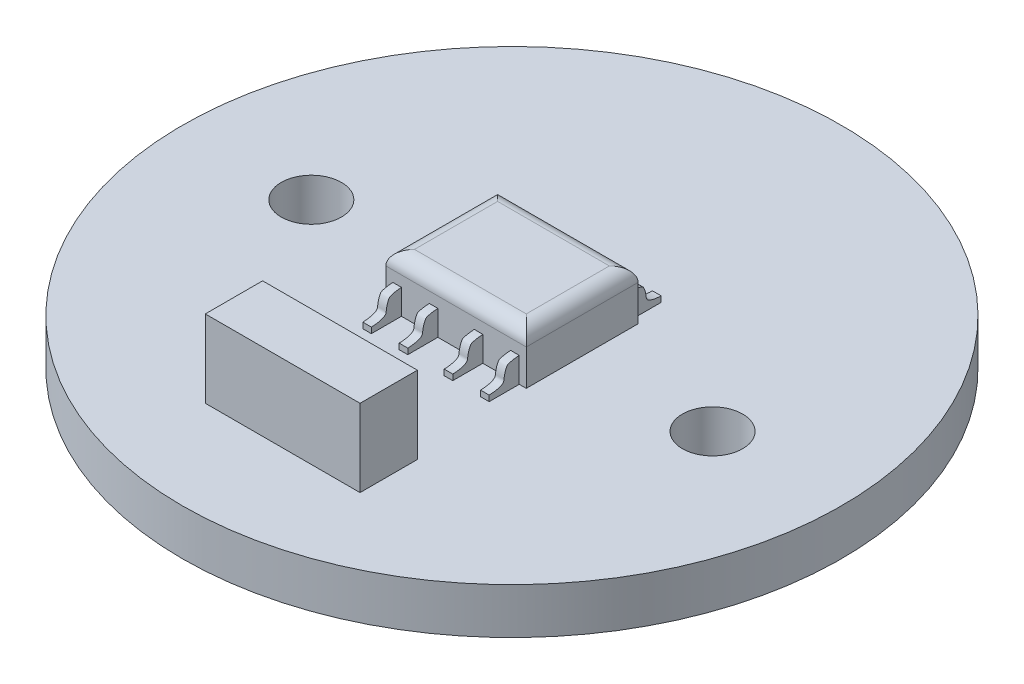
SolidWorks part; units mm, degrees
ref_plane "Front Plane" through (0, 0, 0) normal (0, 0, 1) x (1, 0, 0)
ref_plane "Top Plane" through (0, 0, 0) normal (0, 1, 0) x (1, 0, 0)
ref_plane "Right Plane" through (0, 0, 0) normal (1, 0, 0) x (0, 0, -1)
sketch "Sketch1" plane through (0, 0, 0) normal (0, 1, 0) x (1, 0, 0)
  circle A0 centre (0, 0) radius 11.5
  circle A1 centre (0, 0) radius 7 construction
  circle A2 centre (-7, 0) radius 1.05
  circle A3 centre (7, 0) radius 1.05
  dimension "D1" = 23
  dimension "D2" = 14
  dimension "D3" = 2.1
extrude "Boss-Extrude1" add sketch "Sketch1" along normal blind 1.6
sketch "Sketch2" plane through (0, 1.6, 0) normal (0, 1, 0) x (1, 0, 0)
  line L0 (0, -0.88) -> (0, 0.88) construction
  line L1 (-2.45, 1.95) -> (2.45, 1.95)
  line L2 (-2.45, 1.95) -> (-2.45, -1.95)
  line L3 (-2.45, -1.95) -> (2.45, -1.95)
  line L4 (2.45, 1.95) -> (2.45, -1.95)
  line L5 (-2.45, 1.95) -> (2.45, -1.95) construction
  line L6 (-2.45, -1.95) -> (2.45, 1.95) construction
  point P0 (0, 0)
  dimension "D1" = 4.9
  dimension "D2" = 3.9
extrude "Boss-Extrude2" add sketch "Sketch2" along normal blind 1.75
sketch "Sketch3" plane through (0, 1.6, 0) normal (0, 1, 0) x (1, 0, 0)
  line L0 (-2.45, -1.95) -> (2.45, -1.95) construction
  line L1 (-2.205, -1.95) -> (-1.905, -1.95)
  line L2 (-2.205, -1.95) -> (-2.205, -3)
  line L3 (-2.205, -3) -> (-1.905, -3)
  line L4 (-1.905, -1.95) -> (-1.905, -3)
  line L5 (0, -0.88) -> (0, 0.88) construction
  line L6 (-0.935, -1.95) -> (-0.635, -1.95)
  line L7 (-0.935, -1.95) -> (-0.935, -3)
  line L8 (-0.935, -3) -> (-0.635, -3)
  line L9 (-0.635, -1.95) -> (-0.635, -3)
  point P10 (-2.055, -3)
  point P11 (-0.785, -3)
  dimension "D1" = 1.05
  dimension "D2" = 1.27
  dimension "D3" = 0.3
  dimension "D4" = 0.635
extrude "Boss-Extrude3" add sketch "Sketch3" along normal blind 0.875
mirror "Mirror1" about plane through (0, 0, 0) normal (1, 0, 0) of "Boss-Extrude3"
mirror "Mirror2" about plane through (0, 0, 0) normal (0, 0, 1) of "Mirror1"
fillet "Fillet1" radius 0.5 4 edges at (0, 3.35, 1.95) (-2.45, 3.35, 0) (0, 3.35, -1.95) (2.45, 3.35, 0)
sketch "Sketch4" plane through (2.205, 0, 0) normal (1, 0, 0) x (0, 0, -1)
  line L1 (3, 2.475) -> (3, 1.6) construction
  line L5 (1.95, 2.475) -> (3, 2.475)
  line L6 (3, 2.475) -> (3, 1.8)
  spline S0 degree 3 poles (1.95, 2.475) (2.1128, 2.4691) (2.3554, 2.4188) (2.4061, 2.3158) (2.472, 2.178) (2.4908, 1.8708) (2.8009, 1.8006) (3, 1.8) knots 0 0 0 0 0.320657 0.400503 0.754238 0.818609 1 1 1 1
extrude "Cut-Extrude1" cut sketch "Sketch4" against normal through all both and the other way through all
mirror "Mirror3" about plane through (0, 0, 0) normal (0, 0, 1) of "Cut-Extrude1"
sketch "Sketch5" plane through (0, 1.6, 0) normal (0, 1, 0) x (1, 0, 0)
  line L0 (0, -0.88) -> (0, 0.88) construction
  line L1 (2.7, -8) -> (-2.7, -8)
  line L2 (2.7, -8) -> (2.7, -6)
  line L3 (2.7, -6) -> (-2.7, -6)
  line L4 (-2.7, -8) -> (-2.7, -6)
  line L5 (2.7, -8) -> (-2.7, -6) construction
  line L6 (2.7, -6) -> (-2.7, -8) construction
  circle A0 centre (0, 0) radius 11.5 construction
  point P0 (0, -7)
  dimension "D3" = 3.5
  dimension "D1" = 2
  dimension "D2" = 5.4
extrude "Boss-Extrude4" add sketch "Sketch5" along normal blind 2.7
